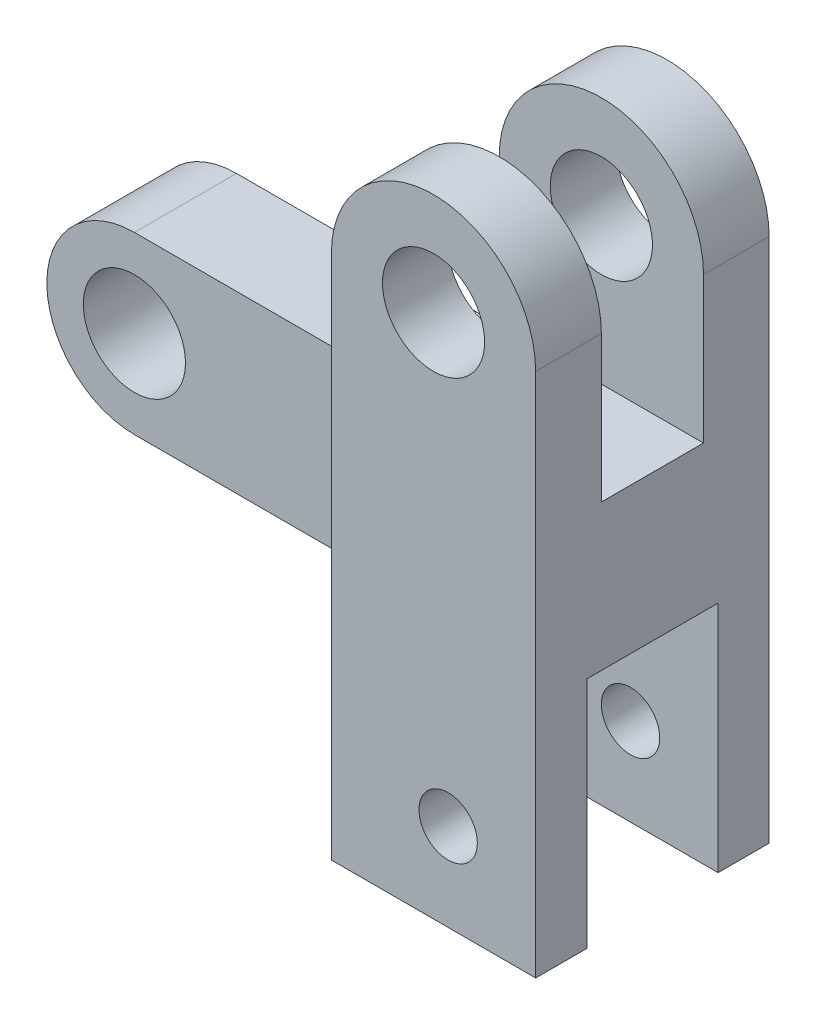
SolidWorks part; units mm, degrees
ref_plane "前视基准面" through (0, 0, 0) normal (0, 0, 1) x (1, 0, 0)
ref_plane "上视基准面" through (0, 0, 0) normal (0, 1, 0) x (1, 0, 0)
ref_plane "右视基准面" through (0, 0, 0) normal (1, 0, 0) x (0, 0, -1)
other "Configuration Table"
sketch "草图1" plane through (0, 0, 0) normal (0, 1, 0) x (1, 0, 0)
  line L1 (0, 3.5) -> (7, 3.5)
  line L2 (0, -3.5) -> (7, -3.5)
  line L3 (0, 3.5) -> (7, 3.5) construction
  line L4 (7, 3.5) -> (7, -3.5)
  line L5 (0, 3.5) -> (0, -3.5)
  dimension "D1" = 7
  dimension "D4" = 90
  dimension "D5" = 7
extrude "凸台-拉伸1" add sketch "草图1" along normal blind 2.4
sketch "草图10" plane through (0, 0, -3.5) normal (0, 0, -1) x (-1, 0, 0)
  line L3 (-7, 2.4) -> (0, 2.4) construction
  line L6 (-7, 2.4) -> (0, 2.4)
  line L7 (0, 2.4) -> (0, 10)
  line L9 (-7, 10) -> (-7, 2.4)
  line L10 (0, 2.4) -> (0, 0) construction
  arc A1 (0, 10) -> (-7, 10) centre (-3.5, 10) ccw
  line M3 (0, 2.4) -> (-7, 2.4)
  dimension "D8" = 3.5
  dimension "D9" = 10
extrude "凸台-拉伸6" add sketch "草图10" against normal blind 1.75 contours L7 A1 L9 M3 region at (3.5, 7.6039, -3.5)
extrude "凸台-拉伸8" add sketch "草图10<2>" along normal blind 1.75 from offset 7 contours L7 A1 L9 M3 region at (3.5, 7.6039, -3.5) offset against normal yes
sketch "草图10<2>" plane through (0, 0, -3.5) normal (0, 0, -1) x (-1, 0, 0) same geometry as "草图10"
sketch "草图11" plane through (0, 0, -3.5) normal (0, 0, -1) x (-1, 0, 0)
  circle A2 centre (-3.5, 10) radius 1.75
  dimension "D3" = 3.5
extrude "切除-拉伸1" cut sketch "草图11" against normal through all
sketch "草图17" plane through (0, 0, 0) normal (0, -1, 0) x (1, 0, 0)
  line L6 (0, 3.5) -> (0, -3.5)
  line L7 (0, -3.5) -> (7, -3.5)
  line L8 (7, -3.5) -> (7, 3.5)
  line L9 (7, 3.5) -> (0, 3.5)
  line L12 (0, 3.5) -> (0, -3.5)
  line L13 (0, -3.5) -> (7, -3.5)
  line L14 (7, -3.5) -> (7, 3.5)
  line L15 (7, 3.5) -> (0, 3.5)
  dimension "D1" = 0
extrude "凸台-拉伸10" add sketch "草图17" along normal blind 8
sketch "草图15" plane through (0, 0, 0) normal (0, 0, 1) x (1, 0, 0)
  line L2 (7, 5) -> (7, -1)
  line L10 (7, 10) -> (7, -8) construction
  line L14 (-9, 5) -> (7, 5)
  line L15 (7, 10) -> (7, -8) construction
  line L17 (7, 2.4) -> (7.3779, 2.4)
  line L18 (0, 2.4) -> (7, 2.4) construction
  line L19 (-9, -1) -> (7, -1)
  line L20 (7, -8) -> (0, -8) construction
  arc A0 (-9, -1) -> (-9, 5) centre (-9, 2) cw
  circle A1 centre (-9, 2) radius 1.75
  dimension "D3" = 3.5
  dimension "D1" = 3
  dimension "D2" = 7
  dimension "D4" = 16
extrude "凸台-拉伸9" add sketch "草图15" along normal mid plane 3.5 contours A0 L19 L2 L14 A1 region at (-1.5385, 2, 0)
sketch "草图12" plane through (0, 4, 3.5) normal (0, 0, -1) x (1, 0, 0)
  line L0 (0, 12) -> (7, 12) construction
  line L2 (7, -6) -> (7, 12) construction
  circle A0 centre (4, 9) radius 1
  dimension "D2" = 2
  dimension "D1" = 3
  dimension "D3" = 3
extrude "切除-拉伸2" cut sketch "草图12" along normal through all
sketch "草图18" plane through (7.4, -8, 0) normal (0, 1, 0) x (1, 0, 0)
  line L0 (-0.4, 1.75) -> (-0.4, 3.5) construction
  line L11 (-7.4, -2.25) -> (-0.4, -2.25)
  line L12 (-7.4, -2.25) -> (-7.4, 2.25)
  line L13 (-7.4, 2.25) -> (-0.4, 2.25)
  line L14 (-0.4, -2.25) -> (-0.4, 2.25)
  point P4 (-7.4, 0)
  dimension "D1" = 4.5
  dimension "D2" = 7
extrude "切除-拉伸4" cut sketch "草图18" along normal blind 8
sketch "草图19" plane through (0, 0, 3.5) normal (0, 0, 1) x (1, 0, 0)
  line L4 (0, 10) -> (0, -8)
  line L5 (0, -8) -> (7, -8)
  line L6 (7, -8) -> (7, 10)
  line L8 (0, 10) -> (0, -8)
  line L9 (0, -8) -> (7, -8)
  line L10 (7, -8) -> (7, 10)
  circle A0 centre (4, -5) radius 1 construction
  circle A1 centre (4, -5) radius 1
  circle A2 centre (3.5, 10) radius 1.75 construction
  arc A3 (7, 10) -> (0, 10) centre (3.5, 10) ccw
  arc A4 (7, 10) -> (0, 10) centre (3.5, 10) ccw
  circle A5 centre (3.5, 10) radius 1.75
  dimension "D1" = 0
extrude "凸台-拉伸11" add sketch "草图19" along normal blind 0.5
sketch "草图20" plane through (0, 0, -3.5) normal (0, 0, -1) x (-1, 0, 0)
  line L4 (-7, 10) -> (-7, -8)
  line L5 (-7, -8) -> (0, -8)
  line L6 (0, -8) -> (0, 10)
  line L8 (-7, 10) -> (-7, -8)
  line L9 (-7, -8) -> (0, -8)
  line L10 (0, -8) -> (0, 10)
  circle A0 centre (-4, -5) radius 1 construction
  circle A1 centre (-4, -5) radius 1
  circle A2 centre (-3.5, 10) radius 1.75 construction
  arc A3 (0, 10) -> (-7, 10) centre (-3.5, 10) ccw
  arc A4 (0, 10) -> (-7, 10) centre (-3.5, 10) ccw
  circle A5 centre (-3.5, 10) radius 1.75
  dimension "D1" = 0
extrude "凸台-拉伸12" add sketch "草图20" along normal blind 0.5
